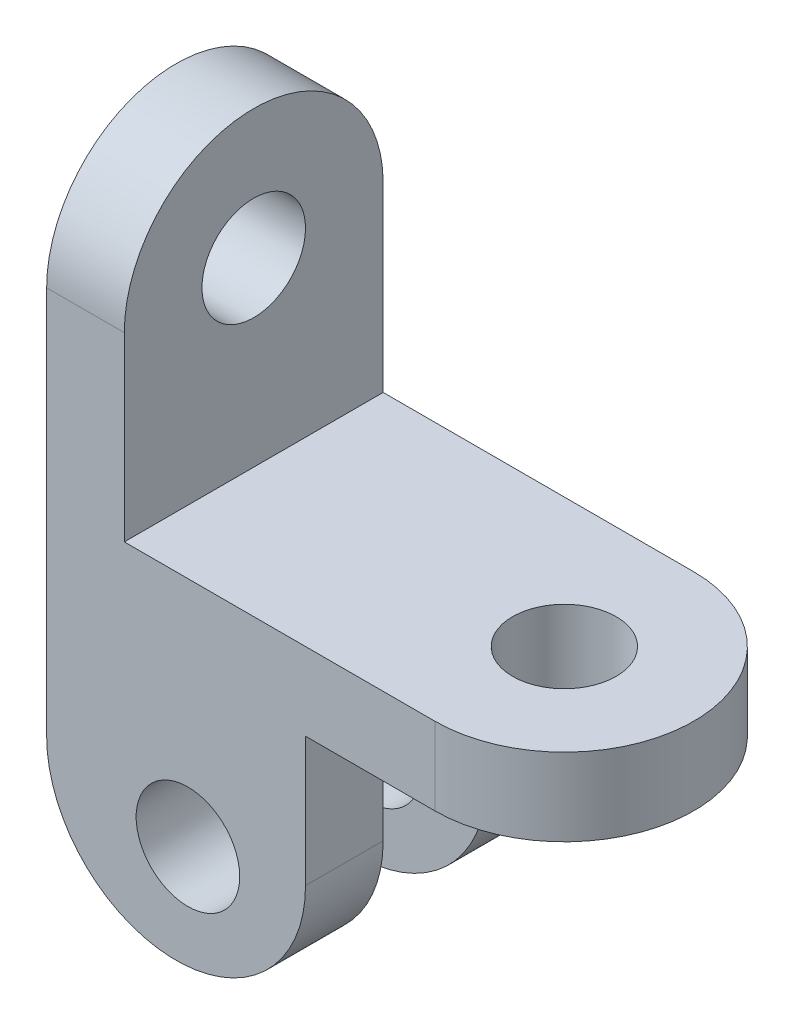
SolidWorks part; units mm, degrees
ref_plane "Front Plane" through (0, 0, 0) normal (0, 0, 1) x (1, 0, 0)
ref_plane "Top Plane" through (0, 0, 0) normal (0, 1, 0) x (1, 0, 0)
ref_plane "Right Plane" through (0, 0, 0) normal (1, 0, 0) x (0, 0, -1)
sketch "Sketch1" plane through (0, 0, 0) normal (0, 1, 0) x (1, 0, 0)
  line L1 (0, 20) -> (-60, 20)
  line L3 (0, -20) -> (-60, -20)
  line L4 (-60, 20) -> (-60, -20)
  arc A0 (0, -20) -> (0, 20) centre (0, 0) ccw
  point P7 (0, -27.0424)
  dimension "D2" = 20
  dimension "D1" = 60
extrude "Boss-Extrude1" add sketch "Sketch1" along normal blind 12
sketch "Sketch2" plane through (0, 12, 0) normal (0, 1, 0) x (1, 0, 0)
  circle A0 centre (0, 0) radius 8
  dimension "D1" = 16
extrude "Cut-Extrude1" cut sketch "Sketch2" against normal through all
sketch "Sketch4" plane through (-60, 0, 0) normal (-1, 0, 0) x (0, 0, 1)
  line L0 (20, 12) -> (20, 0) construction
  line L1 (-20, 12) -> (20, 12)
  line L2 (-20, 12) -> (-20, 40)
  line L4 (20, 12) -> (20, 40)
  arc A0 (20, 40) -> (-20, 40) centre (0, 40) ccw
  dimension "D1" = 28
extrude "Boss-Extrude2" add sketch "Sketch4" against normal blind 12
sketch "Sketch5" plane through (-48, 0, 0) normal (1, 0, 0) x (0, 0, -1)
  circle A0 centre (0, 40) radius 8
  dimension "D1" = 16
extrude "Cut-Extrude2" cut sketch "Sketch5" against normal through all
sketch "Sketch6" plane through (0, 0, 20) normal (0, 0, 1) x (1, 0, 0)
  line L1 (-60, 0) -> (-20, 0)
  line L2 (-60, 0) -> (-60, -20)
  line L4 (-20, 0) -> (-20, -20)
  arc A0 (-60, -20) -> (-20, -20) centre (-40, -20) ccw
  dimension "D1" = 40
  dimension "D2" = 20
extrude "Boss-Extrude3" add sketch "Sketch6" against normal blind 12
sketch "Sketch7" plane through (0, 0, 0) normal (0, -1, 0) x (1, 0, 0)
  line L0 (-60, 0) -> (24.8251, 0) construction
  line L1 (-60, -20) -> (-60, 8) construction
extrude "Boss-Extrude4" add sketch "Sketch6<2>" against normal blind 12 from offset 28 offset against normal yes
sketch "Sketch6<2>" plane through (0, 0, 20) normal (0, 0, 1) x (1, 0, 0) same geometry as "Sketch6"
sketch "Sketch10" plane through (0, 0, 20) normal (0, 0, 1) x (1, 0, 0)
  circle A0 centre (-38.1692, -23.8808) radius 8
  dimension "D1" = 16
extrude "Cut-Extrude3" cut sketch "Sketch10" against normal through all contours A0
